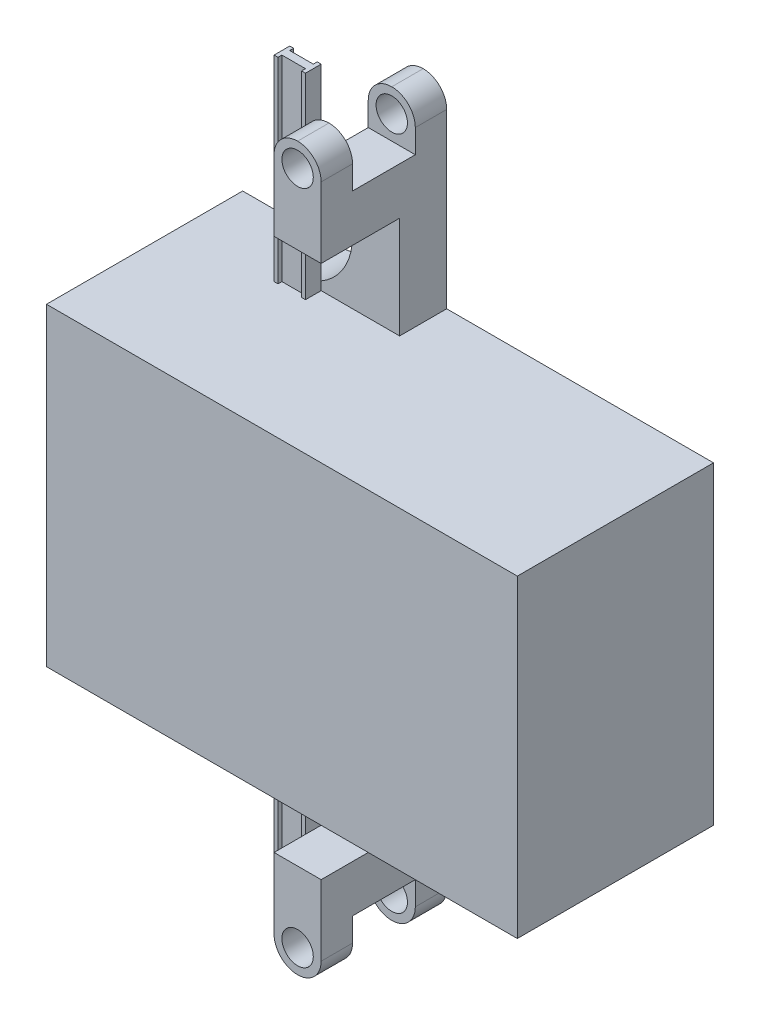
SolidWorks part; units mm, degrees
ref_plane "Front" through (0, 0, 0) normal (0, 0, 1) x (1, 0, 0)
ref_plane "Top" through (0, 0, 0) normal (0, 1, 0) x (1, 0, 0)
ref_plane "Right" through (0, 0, 0) normal (1, 0, 0) x (0, 0, -1)
sketch "Sketch1" plane through (0, 0, 0) normal (0, 0, 1) x (1, 0, 0)
  line L1 (0, 0) -> (-76.2, 0)
  line L2 (0, 0) -> (0, 50.8)
  line L3 (0, 50.8) -> (-76.2, 50.8)
  line L4 (-76.2, 0) -> (-76.2, 50.8)
  dimension "D1" = 76.2
  dimension "D2" = 50.8
extrude "Boss-Extrude1" add sketch "Sketch1" along normal blind 31.75
sketch "Sketch4" plane through (0, 50.8, 0) normal (0, 1, 0) x (1, 0, 0)
  line L0 (-76.2, -31.75) -> (-76.2, 0) construction
  line L1 (-60.96, -10.16) -> (-55.88, -10.16)
  line L2 (-60.96, -10.16) -> (-60.96, -7.62)
  line L3 (-60.96, -7.62) -> (-55.88, -7.62)
  line L4 (-55.88, -10.16) -> (-55.88, -7.62)
  line L5 (-50.8, -7.62) -> (-43.18, -7.62)
  line L6 (-50.8, -7.62) -> (-50.8, 0)
  line L7 (-50.8, 0) -> (-43.18, 0)
  line L8 (-43.18, -7.62) -> (-43.18, 0)
  line L10 (0, 0) -> (-76.2, 0) construction
  dimension "D1" = 25.4
  dimension "D2" = 7.62
  dimension "D3" = 7.62
  dimension "D4" = 2.54
  dimension "D5" = 5.08
  dimension "D6" = 5.08
extrude "Boss-Extrude2" add sketch "Sketch4" along normal blind 31.75 and the other way offset from surface (85.09 mm away) 34.29 other way up to face at (-38.1, 0, 15.875)
fillet "Fillet1" radius 10.16 2 edges at (-50.8, 50.8, 3.81) (-50.8, 0, 3.81)
sketch "Sketch5" plane through (0, 0, 7.62) normal (0, 0, 1) x (1, 0, 0)
  line L0 (-50.8, 60.96) -> (-50.8, 82.55) construction
  line L1 (-43.18, 74.93) -> (-50.8, 74.93)
  line L2 (-43.18, 74.93) -> (-43.18, 67.31)
  line L3 (-43.18, 67.31) -> (-50.8, 67.31)
  line L4 (-50.8, 74.93) -> (-50.8, 67.31)
  line L5 (-43.18, -34.29) -> (-43.18, 0) construction
  line L6 (-50.8, -26.67) -> (-43.18, -26.67)
  line L7 (-50.8, -26.67) -> (-50.8, -19.05)
  line L8 (-50.8, -19.05) -> (-43.18, -19.05)
  line L9 (-43.18, -26.67) -> (-43.18, -19.05)
  line L10 (-50.8, 82.55) -> (-43.18, 82.55) construction
  line L11 (-43.18, 50.8) -> (-43.18, 82.55) construction
  line L12 (-43.18, -34.29) -> (-50.8, -34.29) construction
  line L13 (-50.8, -34.29) -> (-50.8, -10.16) construction
  dimension "D1" = 7.62
  dimension "D2" = 7.62
extrude "Boss-Extrude3" add sketch "Sketch5" along normal blind 12.7
sketch "Sketch6" plane through (0, -34.29, 0) normal (0, -1, 0) x (1, 0, 0)
  line L1 (-50.8, 7.62) -> (-43.18, 7.62)
  line L2 (-50.8, 7.62) -> (-50.8, 5.08)
  line L3 (-50.8, 5.08) -> (-43.18, 5.08)
  line L4 (-43.18, 7.62) -> (-43.18, 5.08)
  line L5 (-50.8, 0) -> (-43.18, 0) construction
  dimension "D1" = 5.08
extrude "Cut-Extrude1" cut sketch "Sketch6" against normal up to surface (7.62 mm away) up to face at (-46.99, -26.67, 13.97)
sketch "Sketch7" plane through (0, 82.55, 0) normal (0, 1, 0) x (1, 0, 0)
  line L0 (-50.8, 0) -> (-50.8, -7.62) construction
  line L1 (-43.18, -7.62) -> (-50.8, -7.62)
  line L2 (-43.18, -7.62) -> (-43.18, -5.08)
  line L3 (-43.18, -5.08) -> (-50.8, -5.08)
  line L4 (-50.8, -7.62) -> (-50.8, -5.08)
  line L5 (-43.18, 0) -> (-50.8, 0) construction
  dimension "D1" = 5.08
extrude "Cut-Extrude2" cut sketch "Sketch7" against normal up to surface (7.62 mm away) up to face at (-46.99, 74.93, 13.97)
sketch "Sketch9" plane through (0, -26.67, 0) normal (0, -1, 0) x (-1, 0, 0)
  line L0 (43.18, -20.32) -> (43.18, -5.08) construction
  line L1 (50.8, -20.32) -> (43.18, -20.32)
  line L2 (50.8, -20.32) -> (50.8, -15.24)
  line L3 (50.8, -15.24) -> (43.18, -15.24)
  line L4 (43.18, -20.32) -> (43.18, -15.24)
  dimension "D1" = 5.08
extrude "Boss-Extrude4" add sketch "Sketch9" along normal up to surface (7.62 mm away) up to face at (-46.99, -34.29, 2.54)
sketch "Sketch10" plane through (0, 74.93, 0) normal (0, 1, 0) x (1, 0, 0)
  line L0 (-50.8, -20.32) -> (-50.8, -5.08) construction
  line L1 (-43.18, -20.32) -> (-50.8, -20.32)
  line L2 (-43.18, -20.32) -> (-43.18, -15.24)
  line L3 (-43.18, -15.24) -> (-50.8, -15.24)
  line L4 (-50.8, -20.32) -> (-50.8, -15.24)
  dimension "D1" = 5.08
extrude "Boss-Extrude5" add sketch "Sketch10" along normal up to surface (7.62 mm away) up to face at (-46.99, 82.55, 2.54)
fillet "Fillet2" radius 3.81 8 edges at (-43.18, 82.55, 2.54) (-50.8, 82.55, 2.54) (-43.18, 82.55, 17.78) (-50.8, 82.55, 17.78) (-50.8, -34.29, 2.54) (-43.18, -34.29, 2.54) (-50.8, -34.29, 17.78) (-43.18, -34.29, 17.78)
sketch "Sketch11" plane through (0, 0, 20.32) normal (0, 0, 1) x (1, 0, 0)
  circle A0 centre (-46.99, 78.74) radius 2.54
  arc A1 (-43.18, 78.74) -> (-46.99, 82.55) centre (-46.99, 78.74) ccw construction
  dimension "D1" = 1.27
extrude "Cut-Extrude3" cut sketch "Sketch11" against normal up to surface (20.32 mm away) up to face at (-46.2507, 24.9238, 0)
sketch "Sketch12" plane through (0, 0, 20.32) normal (0, 0, 1) x (1, 0, 0)
  circle A0 centre (-46.99, -30.48) radius 2.54
  arc A1 (-46.99, -34.29) -> (-43.18, -30.48) centre (-46.99, -30.48) ccw construction
  dimension "D1" = 1.27
extrude "Cut-Extrude4" cut sketch "Sketch12" against normal up to surface (20.32 mm away) up to face at (-44.45, 78.74, 0)
sketch "Sketch13" plane through (0, 82.55, 0) normal (0, 1, 0) x (1, 0, 0)
  line L0 (-60.96, -10.16) -> (-55.88, -10.16) construction
  line L1 (-56.515, -10.16) -> (-60.325, -10.16)
  line L2 (-56.515, -10.16) -> (-56.515, -9.525)
  line L3 (-56.515, -9.525) -> (-60.325, -9.525)
  line L4 (-60.325, -10.16) -> (-60.325, -9.525)
  line L5 (-55.88, -7.62) -> (-60.96, -7.62) construction
  line L6 (-60.325, -7.62) -> (-56.515, -7.62)
  line L7 (-60.325, -7.62) -> (-60.325, -8.255)
  line L8 (-60.325, -8.255) -> (-56.515, -8.255)
  line L9 (-56.515, -7.62) -> (-56.515, -8.255)
  line L10 (-60.96, -7.62) -> (-60.96, -10.16) construction
  line L11 (-55.88, -10.16) -> (-55.88, -7.62) construction
  point P16 (0, 0)
  dimension "D1" = 0.635
  dimension "D2" = 0.635
  dimension "D3" = 0.635
  dimension "D4" = 0.635
extrude "Cut-Extrude5" cut sketch "Sketch13" against normal up to surface (31.75 mm away) up to face at (-48.4909, 50.8, 9.6982)
sketch "Sketch14" plane through (0, -34.29, 0) normal (0, -1, 0) x (-1, 0, 0)
  line L0 (55.88, -10.16) -> (60.96, -10.16) construction
  line L1 (60.325, -10.16) -> (56.515, -10.16)
  line L2 (60.325, -10.16) -> (60.325, -9.525)
  line L3 (60.325, -9.525) -> (56.515, -9.525)
  line L4 (56.515, -10.16) -> (56.515, -9.525)
  line L5 (60.96, -7.62) -> (55.88, -7.62) construction
  line L6 (56.515, -7.62) -> (60.325, -7.62)
  line L7 (56.515, -7.62) -> (56.515, -8.255)
  line L8 (56.515, -8.255) -> (60.325, -8.255)
  line L9 (60.325, -7.62) -> (60.325, -8.255)
  line L10 (60.96, -10.16) -> (60.96, -7.62) construction
  line L11 (55.88, -7.62) -> (55.88, -10.16) construction
  dimension "D1" = 0.635
  dimension "D2" = 0.635
  dimension "D3" = 0.635
  dimension "D4" = 0.635
  dimension "D5" = 0.635
  dimension "D6" = 0.635
extrude "Cut-Extrude6" cut sketch "Sketch14" against normal up to surface (34.29 mm away) up to face at (-48.4909, 0, 9.6982)
